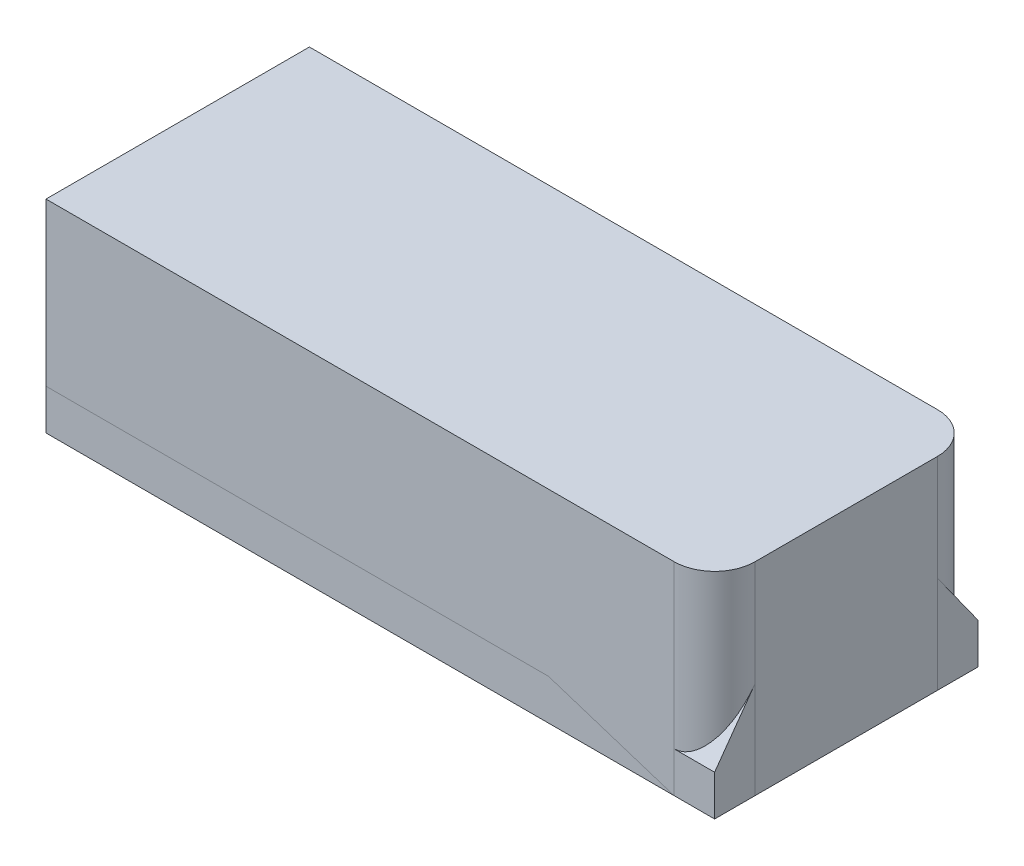
SolidWorks part; units mm, degrees
ref_plane "Front Plane" through (0, 0, 0) normal (0, 0, 1) x (1, 0, 0)
ref_plane "Top Plane" through (0, 0, 0) normal (0, 1, 0) x (1, 0, 0)
ref_plane "Right Plane" through (0, 0, 0) normal (1, 0, 0) x (0, 0, -1)
sketch "Sketch1" plane through (0, 0, 0) normal (0, 1, 0) x (1, 0, 0)
  line L0 (0, -10.3187) -> (0, 10.3187)
  line L1 (0, 10.3187) -> (49.2125, 10.3187)
  line L2 (52.3875, 7.1438) -> (52.3875, -7.1437)
  line L3 (49.2125, -10.3187) -> (0, -10.3187)
  arc A0 (49.2125, 10.3187) -> (52.3875, 7.1438) centre (49.2125, 7.1437) cw
  arc A1 (52.3875, -7.1437) -> (49.2125, -10.3187) centre (49.2125, -7.1437) cw
  point P3 (0, 0)
  point P4 (0, 0)
  point P11 (46.0375, 10.3187)
  dimension "D4" = 3.175
  dimension "D1" = 20.6375
  dimension "D2" = 46.0375
  dimension "D3" = 6.35
sketch "Sketch2" plane through (0, 0, 0) normal (0, 0, 1) x (1, 0, 0)
  line L0 (0, 0) -> (0, 3.175)
  line L1 (0, 3.175) -> (1.5875, 3.175)
  line L2 (1.5875, 3.175) -> (1.5875, 15.875)
  line L3 (1.5875, 15.875) -> (4.7625, 15.875)
  line L4 (4.7625, 15.875) -> (4.7625, 3.175)
  line L5 (4.7625, 3.175) -> (9.525, 3.175)
  line L6 (9.525, 3.175) -> (9.525, 15.875)
  line L7 (9.525, 15.875) -> (12.7, 15.875)
  line L8 (12.7, 15.875) -> (12.7, 3.175)
  line L9 (12.7, 3.175) -> (52.3875, 3.175)
  line L10 (52.3875, 3.175) -> (52.3875, 0)
  line L11 (52.3875, 0) -> (0, 0)
  dimension "D1" = 3.175
  dimension "D2" = 1.5875
  dimension "D3" = 12.7
  dimension "D4" = 3.175
  dimension "D5" = 4.7625
  dimension "D6" = 52.3875
sketch "Sketch3" plane through (0, 0, 0) normal (1, 0, 0) x (0, 0, -1)
  line L0 (10.3188, 0) -> (-10.3187, 0)
  line L1 (-10.3187, 0) -> (-10.3187, 3.175)
  line L2 (-10.3187, 3.175) -> (-1.936, 14.8802)
  line L3 (1.936, 14.8802) -> (10.3187, 3.175)
  line L4 (10.3187, 3.175) -> (10.3188, 0)
  arc A0 (-1.936, 14.8802) -> (1.936, 14.8802) centre (0, 13.4938) cw
  circle A1 centre (0, 13.4938) radius 0.7937
  point P4 (0, 0)
  point P10 (0, 0)
  point P11 (0, 0)
  point P12 (-7.4985, 10.5876)
  dimension "D4" = 2.3813
  dimension "D5" = 1.5875
  dimension "D1" = 20.6375
  dimension "D2" = 3.175
  dimension "D3" = 10.3187
extrude "Boss-Extrude1" add sketch "Sketch1" along normal blind 15.875
extrude "Boss-Extrude2" add sketch "Sketch2" along normal blind 10.3187 and the other way blind 10.3187 separate body
extrude "Boss-Extrude3" add sketch "Sketch3" along normal blind 52.3875 separate body
